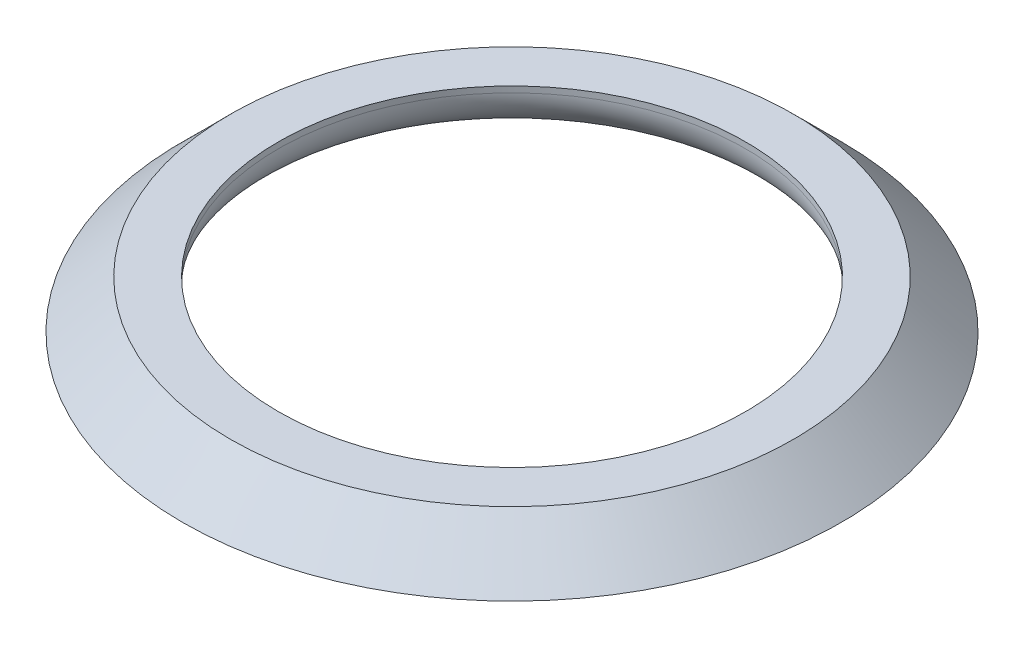
SolidWorks part; units mm, degrees
ref_plane "Front Plane" through (0, 0, 0) normal (0, 0, 1) x (1, 0, 0)
ref_plane "Top Plane" through (0, 0, 0) normal (0, 1, 0) x (1, 0, 0)
ref_plane "Right Plane" through (0, 0, 0) normal (1, 0, 0) x (0, 0, -1)
sketch "Sketch1" plane through (0, 0, 0) normal (0, 1, 0) x (1, 0, 0)
  circle A0 centre (0, 0) radius 9.75
  circle A1 centre (0, 0) radius 13.75
  dimension "D1" = 19.5
  dimension "D2" = 4
extrude "Boss-Extrude1" add sketch "Sketch1" along normal blind 2
chamfer "Chamfer1" distance 2 angle 45 1 edges at (0, 2, 13.75)
fillet "Fillet1" radius 1.75 1 edges at (0, 0, 9.75)
